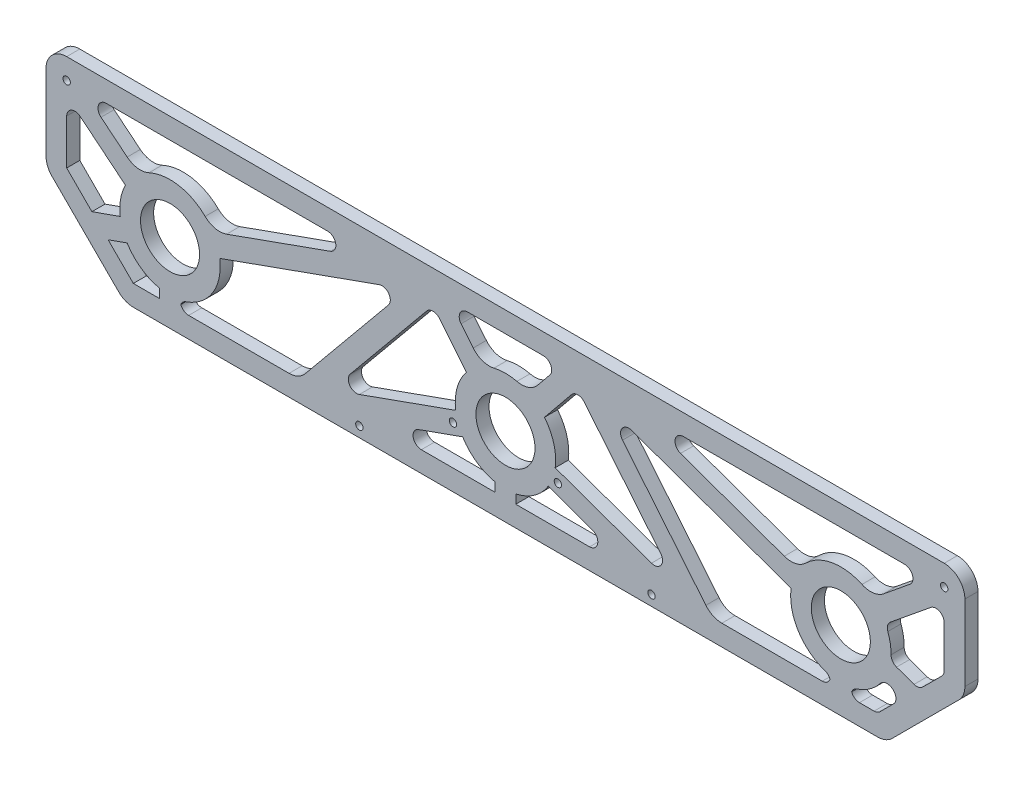
SolidWorks part; units mm, degrees
material "6061 Alloy"
ref_plane "Front Plane" through (0, 0, 0) normal (0, 0, 1) x (1, 0, 0)
ref_plane "Top Plane" through (0, 0, 0) normal (0, 1, 0) x (1, 0, 0)
ref_plane "Right Plane" through (0, 0, 0) normal (1, 0, 0) x (0, 0, -1)
sketch "Sketch1" plane through (0, 0, 0) normal (0, 0, 1) x (1, 0, 0)
  line L0 (2.9289, 35.1711) -> (35.1711, 2.9289)
  line L1 (42.2421, 0) -> (402.2579, 0)
  line L2 (0, 42.2421) -> (0, 78.9)
  line L3 (10, 88.9) -> (434.5, 88.9)
  line L4 (444.5, 42.2421) -> (444.5, 78.9)
  line L5 (409.3289, 2.9289) -> (441.5711, 35.1711)
  line L6 (222.25, 88.9) -> (222.25, 78.9) construction
  line L7 (42.2421, 10) -> (55, 10)
  line L8 (402.2579, 10) -> (414.4609, 22.2031)
  line L9 (434.5, 42.2421) -> (434.5, 72.4466)
  line L10 (17.9086, 78.9) -> (159.3033, 78.9)
  line L11 (10, 42.2421) -> (10, 72.4466)
  line L12 (10, 42.2421) -> (22.2031, 30.0391)
  line L13 (24.4543, 30.8351) -> (22.2031, 30.0391)
  line L14 (30.0391, 22.2031) -> (42.2421, 10)
  line L15 (10, 42.2421) -> (42.2421, 10) construction
  line L16 (44.7466, 57.0002) -> (17.9086, 78.9)
  line L17 (30.0391, 22.2031) -> (39.259, 25.463)
  line L18 (55, 14.3327) -> (55, 10)
  line L19 (38.4244, 49.2523) -> (10, 72.4466)
  line L20 (24.4543, 30.8351) -> (35.9254, 34.891)
  line L21 (65, 14.3327) -> (65, 10)
  line L22 (399.7534, 57.0002) -> (426.5914, 78.9)
  line L23 (65, 10) -> (128.7681, 10)
  line L24 (10, 78.9) -> (434.5, 78.9) construction
  line L25 (42.2421, 10) -> (402.2579, 10) construction
  line L26 (10, 42.2421) -> (10, 78.9) construction
  line L27 (185.1403, 75.7423) -> (203.3633, 53.37)
  line L28 (175.8429, 74.1917) -> (184.0222, 77.1149)
  line L29 (80.6981, 50.8071) -> (159.3033, 78.9)
  line L30 (84.0636, 41.3904) -> (175.8429, 74.1917)
  line L31 (158.4819, 10) -> (201.5519, 25.3929)
  line L32 (141.9423, 14.7083) -> (198.1864, 34.8096)
  line L33 (195.4658, 78.9) -> (211.1167, 59.6855)
  line L34 (185.1403, 75.7423) -> (184.0222, 77.1149)
  line L35 (406.0756, 49.2523) -> (434.5, 72.4466)
  line L36 (195.4658, 78.9) -> (249.0342, 78.9)
  line L37 (158.4819, 10) -> (217.25, 10)
  line L38 (217.25, 14.3327) -> (217.25, 10)
  line L39 (141.9423, 14.7083) -> (128.7681, 10)
  line L40 (420.0457, 30.8351) -> (422.2969, 30.0391)
  line L41 (420.0457, 30.8351) -> (408.5746, 34.891)
  line L42 (379.5, 14.3327) -> (379.5, 10)
  line L43 (389.5, 14.3327) -> (389.5, 10)
  line L44 (414.4609, 22.2031) -> (405.241, 25.463)
  line L45 (414.4609, 22.2031) -> (402.2579, 10)
  line L46 (402.2579, 10) -> (389.5, 10)
  line L47 (379.5, 10) -> (315.7319, 10)
  line L48 (286.0181, 10) -> (227.25, 10)
  line L49 (302.5577, 14.7083) -> (315.7319, 10)
  line L50 (302.5577, 14.7083) -> (246.3136, 34.8096)
  line L51 (286.0181, 10) -> (242.9481, 25.3929)
  line L52 (363.8019, 50.8071) -> (285.1967, 78.9)
  line L53 (360.4364, 41.3904) -> (268.6571, 74.1917)
  line L54 (268.6571, 74.1917) -> (260.4778, 77.1149)
  line L55 (259.3597, 75.7423) -> (260.4778, 77.1149)
  line L56 (249.0342, 78.9) -> (233.3833, 59.6855)
  line L57 (259.3597, 75.7423) -> (241.1367, 53.37)
  line L58 (285.1967, 78.9) -> (426.5914, 78.9)
  line L59 (422.2969, 30.0391) -> (434.5, 42.2421)
  line L60 (402.2579, 10) -> (434.5, 42.2421) construction
  line L61 (434.5, 42.2421) -> (434.5, 78.9) construction
  line L62 (227.25, 10) -> (227.25, 14.3327)
  arc A0 (434.5, 88.9) -> (444.5, 78.9) centre (434.5, 78.9) cw
  arc A1 (441.5711, 35.1711) -> (444.5, 42.2421) centre (434.5, 42.2421) ccw
  arc A2 (409.3289, 2.9289) -> (402.2579, 0) centre (402.2579, 10) cw
  arc A3 (35.1711, 2.9289) -> (42.2421, 0) centre (42.2421, 10) ccw
  arc A4 (2.9289, 35.1711) -> (0, 42.2421) centre (10, 42.2421) cw
  arc A5 (0, 78.9) -> (10, 88.9) centre (10, 78.9) cw
  circle A6 centre (60, 38.1) radius 14.2875
  circle A8 centre (384.5, 38.1) radius 14.2875
  arc A9 (402.2579, 10) -> (402.2579, 10) centre (402.2579, 10) cw
  arc A10 (434.5, 42.2421) -> (434.5, 42.2421) centre (434.5, 42.2421) ccw
  arc A11 (434.5, 78.9) -> (434.5, 78.9) centre (434.5, 78.9) cw
  arc A12 (10, 78.9) -> (10, 78.9) centre (10, 78.9) cw
  arc A13 (10, 42.2421) -> (10, 42.2421) centre (10, 42.2421) cw
  arc A14 (42.2421, 10) -> (42.2421, 10) centre (42.2421, 10) ccw
  arc A15 (38.4244, 49.2523) -> (35.9254, 34.891) centre (60, 38.1) ccw
  arc A16 (201.5519, 25.3929) -> (217.25, 14.3327) centre (222.25, 38.1) ccw
  arc A17 (363.8019, 50.8071) -> (399.7534, 57.0002) centre (384.5, 38.1) cw
  circle A18 centre (60, 38.1) radius 24.2875 construction
  arc A19 (39.259, 25.463) -> (55, 14.3327) centre (60, 38.1) ccw
  arc A20 (65, 14.3327) -> (84.0636, 41.3904) centre (60, 38.1) ccw
  arc A21 (80.6981, 50.8071) -> (44.7466, 57.0002) centre (60, 38.1) ccw
  circle A22 centre (222.25, 38.1) radius 14.2875
  arc A23 (203.3633, 53.37) -> (198.1864, 34.8096) centre (222.25, 38.1) ccw
  arc A24 (227.25, 14.3327) -> (242.9481, 25.3929) centre (222.25, 38.1) ccw
  arc A25 (246.3136, 34.8096) -> (241.1367, 53.37) centre (222.25, 38.1) ccw
  arc A26 (233.3833, 59.6855) -> (211.1167, 59.6855) centre (222.25, 38.1) ccw
  circle A27 centre (384.5, 38.1) radius 24.2875 construction
  arc A28 (406.0756, 49.2523) -> (408.5746, 34.891) centre (384.5, 38.1) cw
  arc A29 (379.5, 14.3327) -> (360.4364, 41.3904) centre (384.5, 38.1) cw
  arc A30 (405.241, 25.463) -> (389.5, 14.3327) centre (384.5, 38.1) cw
  point P0 (0, 0)
  point P3 (444.5, 0)
  point P13 (444.5, 38.1)
  point P16 (406.4, 0)
  point P19 (38.1, 0)
  point P22 (0, 38.1)
  point P25 (0, 88.9)
  dimension "D3" = 10
  dimension "D4" = 28.575
  dimension "D5" = 28.575
  dimension "D1" = 88.9
  dimension "D2" = 444.5
  dimension "D8" = 60
  dimension "D9" = 10
  dimension "D10" = 10
  dimension "D11" = 10
extrude "Boss-Extrude1" add sketch "Sketch1" along normal blind 6.35 contours A5 L2 A4 L0 A3 L1 A2 L5 A1 L4 A0 L3 A30 L44 L8 L46 L43 A29 L42 L47 L49 L50 A25 L57 L55 L54 L53 A28 L35 L9 L59 L40 L41 A22 A17 L52 L58 L22 A6 A8 L19 A15 L20 region at (4.9492, 40.15, 0)
sketch "Sketch2" plane through (0, 0, 6.35) normal (0, 0, 1) x (1, 0, 0)
  line L0 (65, 10) -> (128.7681, 10) construction
  line L1 (128.7681, 10) -> (198.1864, 34.8096) construction
  line L2 (257.2568, 73.1606) -> (306.5554, 13.2796)
  line L3 (174.8458, 73.8353) -> (124.908, 13.178)
  line L4 (269.6542, 73.8353) -> (319.592, 13.178)
  line L5 (187.8824, 73.937) -> (137.9446, 13.2796)
  line L6 (184.0222, 77.1149) -> (203.3633, 53.37) construction
  line L7 (84.0636, 41.3904) -> (184.0222, 77.1149) construction
  line L8 (122.2917, 10) -> (128.7681, 10)
  line L9 (128.7681, 10) -> (137.9446, 13.2796)
  line L10 (184.0222, 77.1149) -> (187.2432, 73.1606)
  line L11 (174.8458, 73.8353) -> (184.0222, 77.1149)
  line L12 (124.908, 13.178) -> (122.2917, 10)
  line L13 (319.592, 13.178) -> (322.2083, 10)
  line L14 (246.3136, 34.8096) -> (315.7319, 10) construction
  line L15 (379.5, 10) -> (315.7319, 10) construction
  line L16 (260.4778, 77.1149) -> (241.1367, 53.37) construction
  line L17 (360.4364, 41.3904) -> (260.4778, 77.1149) construction
  line L18 (306.5554, 13.2796) -> (315.7319, 10)
  line L19 (322.2083, 10) -> (315.7319, 10)
  line L20 (260.4778, 77.1149) -> (257.2568, 73.1606)
  line L21 (269.6542, 73.8353) -> (260.4778, 77.1149)
extrude "Boss-Extrude2" add sketch "Sketch2" against normal up to surface (6.35 mm away) contours L3 L12 L8 L9 L5 L10 L11 | L4 L21 L20 L2 L18 L19 L13 region at (288.5779, 43.0632, 6.35) region at (155.9221, 43.0632, 6.35) up to face at (400.4223, 16.074, 0)
fillet "Fillet1" radius 10 8 edges at (80.6981, 50.8071, 3.175) (44.7466, 57.0002, 3.175) (211.1167, 59.6855, 3.175) (233.3833, 59.6855, 3.175) (122.2917, 10, 3.175) (322.2083, 10, 3.175) (399.7534, 57.0002, 3.175) (363.8019, 50.8071, 3.175)
fillet "Fillet2" radius 4 16 edges at (10, 72.4466, 3.175) (434.5, 72.4466, 3.175) (17.9086, 78.9, 3.175) (159.3033, 78.9, 3.175) (174.8458, 73.8353, 3.175) (269.6542, 73.8353, 3.175) (286.0181, 10, 3.175) (158.4819, 10, 3.175) (137.9446, 13.2796, 3.175) (306.5554, 13.2796, 3.175) (257.2568, 73.1606, 3.175) (187.2432, 73.1606, 3.175) (195.4658, 78.9, 3.175) (249.0342, 78.9, 3.175) (426.5914, 78.9, 3.175) (285.1967, 78.9, 3.175)
fillet "Fillet3" radius 4 13 edges at (434.5, 42.2421, 3.175) (422.2969, 30.0391, 3.175) (408.5746, 34.891, 3.175) (406.0756, 49.2523, 3.175) (414.4609, 22.2031, 3.175) (405.241, 25.463, 3.175) (402.2579, 10, 3.175) (389.5, 10, 3.175) (389.5, 14.3327, 3.175) (65, 10, 3.175) (65, 14.3327, 3.175) (379.5, 14.3327, 3.175) (379.5, 10, 3.175)
sketch "Sketch3" plane through (0, 0, 0) normal (0, 0, -1) x (-1, 0, 0)
  line L0 (-222.25, 88.9) -> (-222.25, 78.9) construction
  line L1 (-10, 88.9) -> (-434.5, 88.9) construction
  line L2 (-203.8829, 78.9) -> (-240.6171, 78.9) construction
  circle A0 centre (-434.5, 78.9) radius 1.778
  circle A2 centre (-247.6206, 29.0327) radius 1.778
  circle A3 centre (-196.8794, 29.0327) radius 1.778
  circle A4 centre (-10, 78.9) radius 1.778
  dimension "D1" = 3.556
  dimension "D2" = 3.556
  dimension "D3" = 3.556
extrude "Cut-Extrude1" cut sketch "Sketch3" against normal blind 10
sketch "Sketch4" plane through (0, 0, 0) normal (0, 0, -1) x (-1, 0, 0)
  line L0 (-42.2421, 0) -> (-402.2579, 0) construction
  circle A0 centre (-292.913, 5) radius 1.778
  circle A1 centre (-151.587, 5) radius 1.778
  dimension "D1" = 3.556
  dimension "D2" = 3.556
  dimension "D3" = 5
  dimension "D4" = 5
  dimension "D5" = 0
  dimension "D6" = 0
extrude "Cut-Extrude2" cut sketch "Sketch4" against normal blind 10
